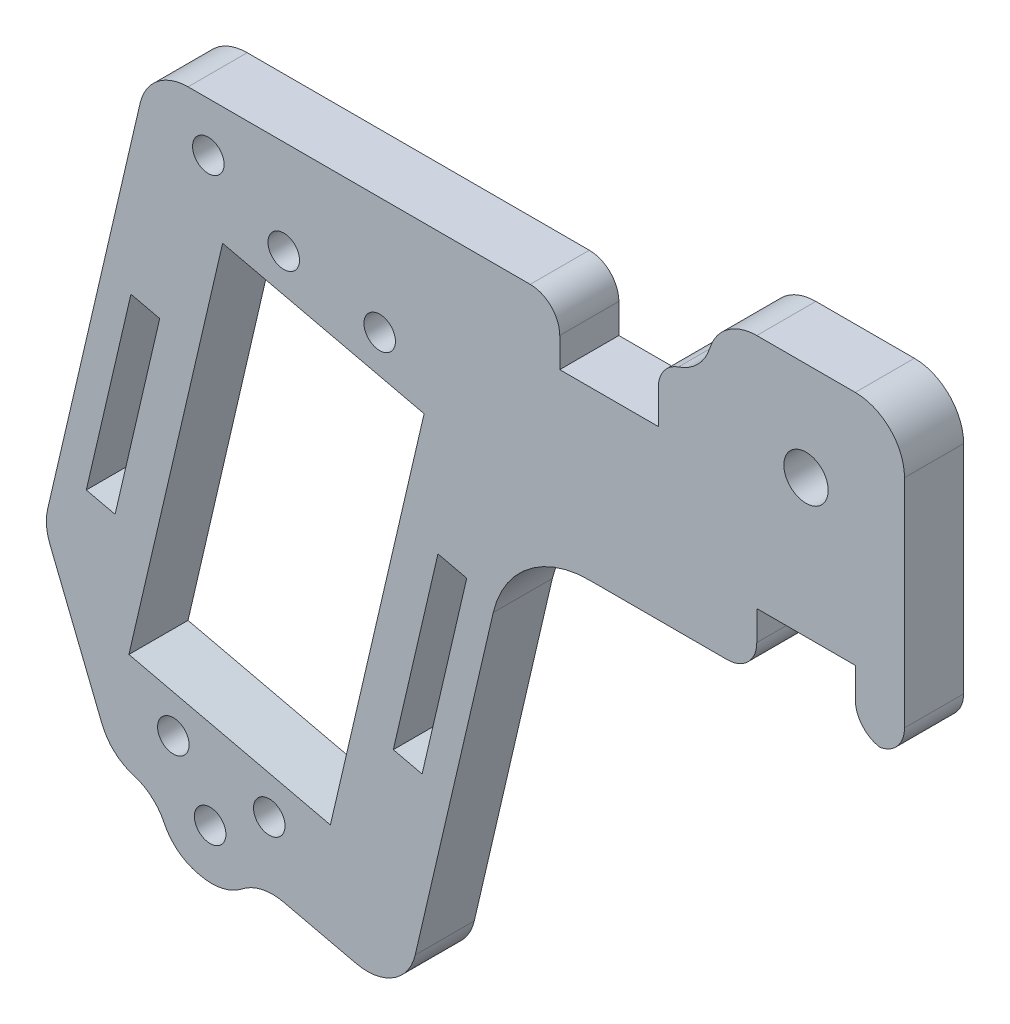
SolidWorks part; units mm, degrees
material "MDF"
ref_plane "Plano frontal" through (0, 0, 0) normal (0, 0, 1) x (1, 0, 0)
ref_plane "Plano superior" through (0, 0, 0) normal (0, 1, 0) x (1, 0, 0)
ref_plane "Plano direito" through (0, 0, 0) normal (1, 0, 0) x (0, 0, -1)
sketch "Esboço1" plane through (0, 0, 0) normal (0, 0, 1) x (1, 0, 0)
  line L0 (0, 20) -> (0, 0) construction
  line L5 (15, 16) -> (18, 16) construction
  line L6 (18, 6) -> (18, 16) construction
  line L15 (10, 11) -> (-10, 11) construction
  line L16 (15, 6) -> (18, 6) construction
  line L21 (-15, 6) -> (-18, 6) construction
  line L22 (-15, 6) -> (-15, 16) construction
  line L27 (-15, 16) -> (-18, 16) construction
  line L28 (-18, 6) -> (-18, 16) construction
  line L29 (-15, 6) -> (-18, 16) construction
  line L30 (-15, 16) -> (-18, 6) construction
  line L35 (15, 6) -> (15, 16) construction
  line L36 (23, 0) -> (23, 23)
  line L37 (23, 23) -> (-66.701, 23)
  line L43 (-29.9553, 0) -> (23, 0)
  line L61 (-68.7379, -29.9136) -> (-59.2257, 10.995)
  line L66 (-59.2257, 10.995) -> (-38.7714, 6.2389)
  line L67 (-38.7714, 6.2389) -> (-48.2836, -34.6697)
  line L68 (-48.2836, -34.6697) -> (-68.7379, -29.9136)
  line L69 (-63.9818, -9.4593) -> (-43.5275, -14.2154) construction
  line L74 (-48.9985, 8.617) -> (-58.5107, -32.2917) construction
  line L75 (-61.7051, 0.3321) -> (-41.2508, -4.424) construction
  line L80 (-38.7714, 6.2389) -> (-38.7714, -27.2218) construction
  line L85 (0, 20) -> (-15.8727, -48.263) construction
  line L86 (5, 0) -> (-5, 0)
  line L87 (-66.701, 23) -> (-80.7429, -37.389)
  line L88 (-80.7429, -37.389) -> (-40.8082, -46.6747)
  line L89 (-40.8082, -46.6747) -> (-29.9553, 0)
  line L93 (-65.6456, -40.8994) -> (-66.4949, -44.552)
  line L94 (-66.4949, -44.552) -> (-56.7548, -46.8168)
  line L95 (-55.9055, -43.1642) -> (-56.7548, -46.8168)
  line L96 (-47.0168, 17.1396) -> (-48.1492, 12.2695) construction
  line L97 (-48.1492, 12.2695) -> (-53.0193, 13.4019) construction
  line L98 (5, 0) -> (5, 6)
  line L99 (5, 6) -> (-5, 6)
  line L100 (-5, 0) -> (-5, 6)
  line L101 (0, 6) -> (0, 0) construction
  line L102 (5, 3) -> (-5, 3) construction
  line L103 (-10, 23) -> (-10, 30)
  line L104 (-10, 30) -> (10, 30)
  line L105 (10, 30) -> (10, 23)
  line L106 (10, 23) -> (10, 0)
  line L107 (-73.0647, -17.6141) -> (-70.1427, -18.2935)
  line L108 (-70.1427, -18.2935) -> (-65.6131, 1.1868)
  line L109 (-65.6131, 1.1868) -> (-68.5351, 1.8662)
  line L110 (-38.9742, -25.5409) -> (-41.8962, -24.8615)
  line L111 (-37.3666, -5.3812) -> (-34.4446, -6.0606)
  line L112 (-41.8962, -24.8615) -> (-37.3666, -5.3812)
  line L113 (-68.5351, 1.8662) -> (-73.0647, -17.6141)
  line L114 (-15, 17) -> (-25, 17)
  line L115 (-15, 17) -> (-15, 23)
  line L116 (-15, 23) -> (-25, 23)
  line L117 (-25, 17) -> (-25, 23)
  line L118 (-20, 23) -> (-20, 17) construction
  line L119 (-15, 20) -> (-25, 20) construction
  line L120 (-34.4446, -6.0606) -> (-38.9742, -25.5409)
  circle A0 centre (0, 20) radius 2.25
  circle A1 centre (10, 11) radius 1.6 construction
  circle A2 centre (-10, 11) radius 1.6 construction
  circle A8 centre (-64.2301, -34.8118) radius 1.6
  circle A9 centre (-54.49, -37.0766) radius 1.6
  circle A10 centre (-43.2792, 11.1371) radius 1.6
  circle A11 centre (-53.0193, 13.4019) radius 1.6
  circle A12 centre (-47.0168, 17.1396) radius 1.6 construction
  circle A15 centre (-60.4925, -40.8143) radius 1.6
  circle A16 centre (-60.6769, 18) radius 1.6
  point P0 (0, 20)
  point P13 (-16.5, 11)
  point P39 (-51.4779, -2.046)
  point P49 (0, 3)
  point P61 (0, 11)
  point P62 (-67.8779, -8.5534)
  point P68 (0, 30)
  point P69 (-20, 20)
  dimension "D1" = 4.5
  dimension "D3" = 3.2
  dimension "D11" = 14.6974
  dimension "D12" = 56
  dimension "D9" = 49.5
  dimension "D30" = 5
  dimension "D33" = 5
  dimension "D34" = 7
  dimension "D2" = 20
  dimension "D4" = 5
  dimension "D5" = 21
  dimension "D6" = 10
  dimension "D7" = 3
  dimension "D8" = 42
  dimension "D10" = 10
  dimension "D13" = 20
  dimension "D14" = 10
  dimension "D15" = 10
  dimension "D16" = 10
  dimension "D17" = 6
  dimension "D18" = 5
  dimension "D19" = 7
  dimension "D20" = 6
  dimension "D21" = 13.09
  dimension "D22" = 10
  dimension "D23" = 10
  dimension "D24" = 5
  dimension "D25" = 5
  dimension "D26" = 20
  dimension "D27" = 3
  dimension "D28" = 20
  dimension "D32" = 4
extrude "Ressalto-extrusão1" add sketch "Esboço1" along normal blind 6 contours L37 L87 L88 L89 L43 A12 A9 A8 A0 L67 L68 L61 L66 L21 L28 L27 L22 L86 L100 L99 L98 A10 A11 | L104 L103 L37 | L95 L88 L93 L94 A15 region at (-39.0316, -2.4357, 0) region at (0, 26.5, 0) region at (-61.2053, -43.8799, 0)
fillet "Filete1" radius 10 1 edges at (-29.9553, 0, 3)
fillet "Filete2" radius 5 6 edges at (-66.701, 23, 3) (-66.4949, -44.552, 3) (-56.7548, -46.8168, 3) (-40.8082, -46.6747, 3) (-10, 30, 3) (10, 30, 3)
fillet "Filete4" radius 5 3 edges at (-65.6456, -40.8994, 3) (-55.9055, -43.1642, 3) (-10, 23, 3)
fillet "Filete5" radius 3 5 edges at (-25, 23, 3) (-15, 23, 3) (-5, 0, 3) (10, 0, 3) (5, 0, 3)
chamfer "Chanfro1" distance 15 angle 35 1 edges at (-80.7429, -37.389, 3) first distance on face at (-74.1716, -9.1283, 3)
fillet "Filete6" radius 5 2 edges at (-77.3457, -22.7787, 3) (-70.5127, -39.7677, 3)
